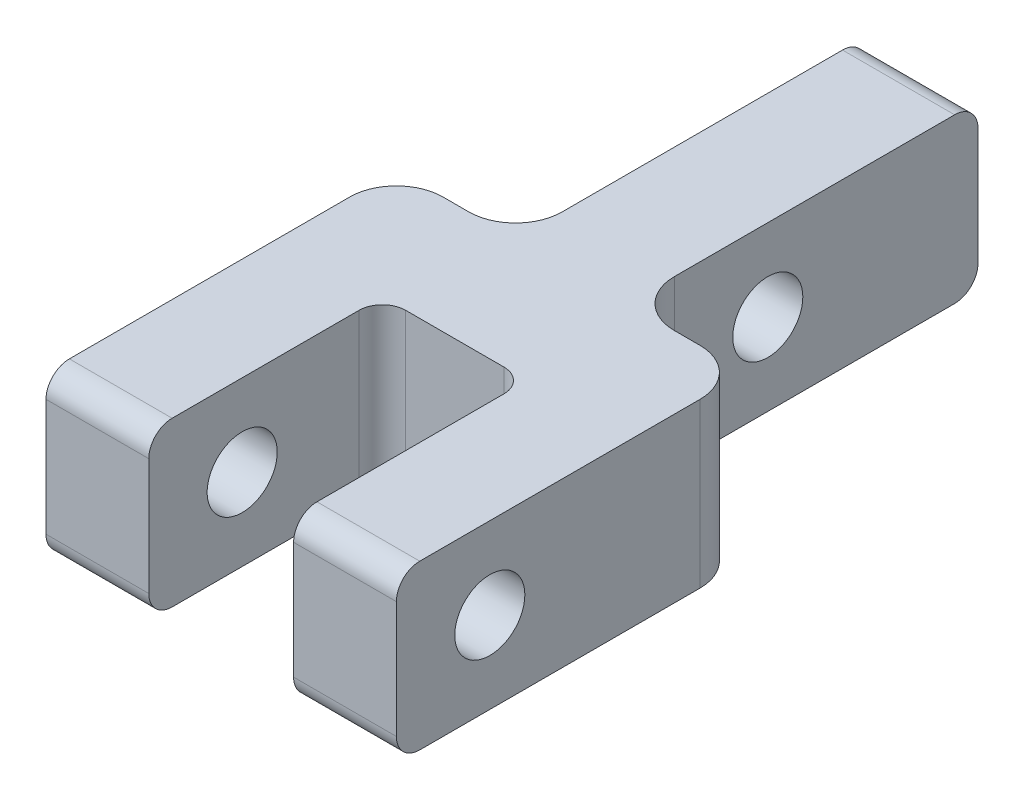
SolidWorks part; units mm, degrees
ref_plane "Alzado" through (0, 0, 0) normal (0, 0, 1) x (1, 0, 0)
ref_plane "Planta" through (0, 0, 0) normal (0, 1, 0) x (1, 0, 0)
ref_plane "Vista lateral" through (0, 0, 0) normal (1, 0, 0) x (0, 0, -1)
sketch "Croquis1" plane through (0, 0, 0) normal (1, 0, 0) x (0, 0, -1)
  line L0 (-14, 3.5) -> (14, 3.5)
  line L2 (-15, 0) -> (15, 0) construction
  line L3 (-15, 2.5) -> (-15, -2.5)
  line L4 (-14, -3.5) -> (14, -3.5)
  line L5 (15, 2.5) -> (15, -2.5)
  arc A0 (-15, -2.5) -> (-14, -3.5) centre (-14, -2.5) ccw
  arc A1 (-15, 2.5) -> (-14, 3.5) centre (-14, 2.5) cw
  arc A2 (14, -3.5) -> (15, -2.5) centre (14, -2.5) ccw
  arc A3 (14, 3.5) -> (15, 2.5) centre (14, 2.5) cw
  point P1 (0, 0)
  point P9 (-15, -3.5)
  point P13 (-15, 3.5)
  point P16 (15, -3.5)
  point P19 (15, 3.5)
  dimension "D3" = 1
  dimension "D4" = 1
  dimension "D1" = 3.5
  dimension "D2" = 30
extrude "Saliente-Extruir1" add sketch "Croquis1" along normal mid plane 4.8
sketch "Croquis2" plane through (0, 0, 0) normal (1, 0, 0) x (0, 0, -1)
  line L0 (-15, 2.5) -> (-15, -2.5) construction
  line L1 (15, -2.5) -> (15, 2.5) construction
  circle A0 centre (-11, 0) radius 1.5
  circle A1 centre (6, 0) radius 1.5
  dimension "D1" = 3
  dimension "D3" = 3
  dimension "D2" = 4
  dimension "D4" = 9
extrude "Cortar-Extruir1" cut sketch "Croquis2" against normal through all both and the other way through all
sketch "Croquis3" plane through (0, 0, 0) normal (1, 0, 0) x (0, 0, -1)
  line L0 (-15, 2.5) -> (-15, -2.5) construction
  line L1 (-15, 2.5) -> (-15, -2.5)
  line L2 (-14, 3.5) -> (0, 3.5)
  line L3 (14, 3.5) -> (-14, 3.5) construction
  line L4 (0, 3.5) -> (0, -3.5)
  line L5 (-14, -3.5) -> (14, -3.5) construction
  line L6 (0, -3.5) -> (-14, -3.5)
  circle A0 centre (-11, 0) radius 1.5 construction
  circle A1 centre (-11, 0) radius 1.5
  arc A2 (-14, 3.5) -> (-15, 2.5) centre (-14, 2.5) ccw construction
  arc A3 (-14, 3.5) -> (-15, 2.5) centre (-14, 2.5) ccw
  arc A4 (-15, -2.5) -> (-14, -3.5) centre (-14, -2.5) ccw construction
  arc A5 (-15, -2.5) -> (-14, -3.5) centre (-14, -2.5) ccw
extrude "Saliente-Extruir2" add sketch "Croquis3" along normal mid plane 15
sketch "Croquis4" plane through (0, 0, 0) normal (1, 0, 0) x (0, 0, -1)
  line L0 (-14, 3.5) -> (-5, 3.5)
  line L1 (0, 3.5) -> (-14, 3.5) construction
  line L2 (-5, 3.5) -> (-5, -3.5)
  line L3 (-14, -3.5) -> (0, -3.5) construction
  line L4 (-15, 2.5) -> (-15, -2.5)
  line L5 (-14, -3.5) -> (0, -3.5)
  line L6 (0, -3.5) -> (0, 3.5)
  line L7 (0, 3.5) -> (-14, 3.5)
  line L8 (-15, 2.5) -> (-15, -2.5)
  line L12 (-5, -3.5) -> (-14, -3.5)
  arc A2 (-14, 3.5) -> (-15, 2.5) centre (-14, 2.5) ccw
  arc A3 (-15, -2.5) -> (-14, -3.5) centre (-14, -2.5) ccw
  arc A4 (-14, 3.5) -> (-15, 2.5) centre (-14, 2.5) ccw
  arc A5 (-15, -2.5) -> (-14, -3.5) centre (-14, -2.5) ccw
  dimension "D2" = 10
  dimension "D1" = 0
extrude "Cortar-Extruir2" cut sketch "Croquis4" against normal mid plane 6.2
fillet "Redondeo1" radius 2 4 edges at (2.4, 0, 0) (-2.4, 0, 0) (7.5, 0, 0) (-7.5, 0, 0)
fillet "Redondeo2" radius 1 2 edges at (3.1, 0, 5) (-3.1, 0, 5)
